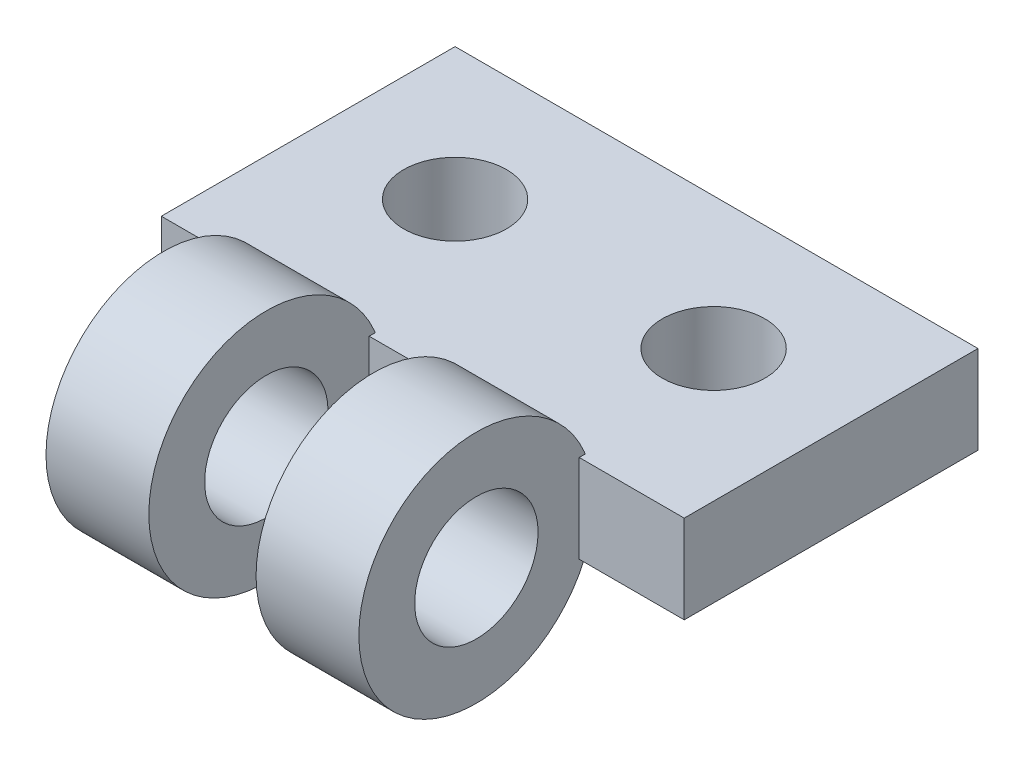
SolidWorks part; units mm, degrees
ref_plane "Alzado" through (0, 0, 0) normal (0, 0, 1) x (1, 0, 0)
ref_plane "Planta" through (0, 0, 0) normal (0, 1, 0) x (1, 0, 0)
ref_plane "Vista lateral" through (0, 0, 0) normal (1, 0, 0) x (0, 0, -1)
sketch "Croquis1" plane through (0, 0, 0) normal (1, 0, 0) x (0, -1, 0)
  circle A0 centre (0, 0) radius 4
  circle A1 centre (0, 0) radius 2.1
  dimension "D1" = 4.2
  dimension "D2" = 8
extrude "Saliente-Extruir1" add sketch "Croquis1" along normal blind 3.5
ref_axis "Eje1" through (3.5, 0, 0) along (-1, 0, 0)
pattern_linear "MatrizL3" count 2 spacing 7.15 along (-1, 0, 0) of bodies 101
ref_plane "Plano1" through (0, 0, -3.5) normal (0, 0, 1) x (1, 0, 0)
ref_plane "Plano2" through (-1.825, 0, 0) normal (1, 0, 0) x (0, 0, -1)
sketch "Croquis4" plane through (0, 0, -3.5) normal (0, 0, 1) x (1, 0, 0)
  line L1 (-10.725, 1.5) -> (7.075, 1.5)
  line L2 (-10.725, 1.5) -> (-10.725, -1.5)
  line L3 (-10.725, -1.5) -> (7.075, -1.5)
  line L4 (7.075, 1.5) -> (7.075, -1.5)
  line L9 (-1.825, -4.4) -> (-1.825, 4.4) construction
  point P4 (-10.725, 0)
  point P8 (-1.825, 1.5)
  dimension "D1" = 3
  dimension "D2" = 17.8
extrude "Saliente-Extruir2" add sketch "Croquis4" against normal blind 10 separate body
ref_plane "Plano3" through (-1.825, 0, 0) normal (1, 0, 0) x (0, 0, -1)
sketch "Croquis5" plane through (0, 1.5, 0) normal (0, 1, 0) x (1, 0, 0)
  line L0 (7.075, 13.5) -> (-10.725, 13.5) construction
  line L1 (7.075, 13.5) -> (7.075, 3.5) construction
  line L2 (-1.825, 13.5) -> (-1.825, 12.0443) construction
  circle A0 centre (2.575, 9) radius 1.75
  circle A1 centre (-6.225, 9) radius 1.75
  dimension "D1" = 3.5
  dimension "D2" = 4.5
  dimension "D3" = 4.5
extrude "Cortar-Extruir1" cut sketch "Croquis5" against normal through all
